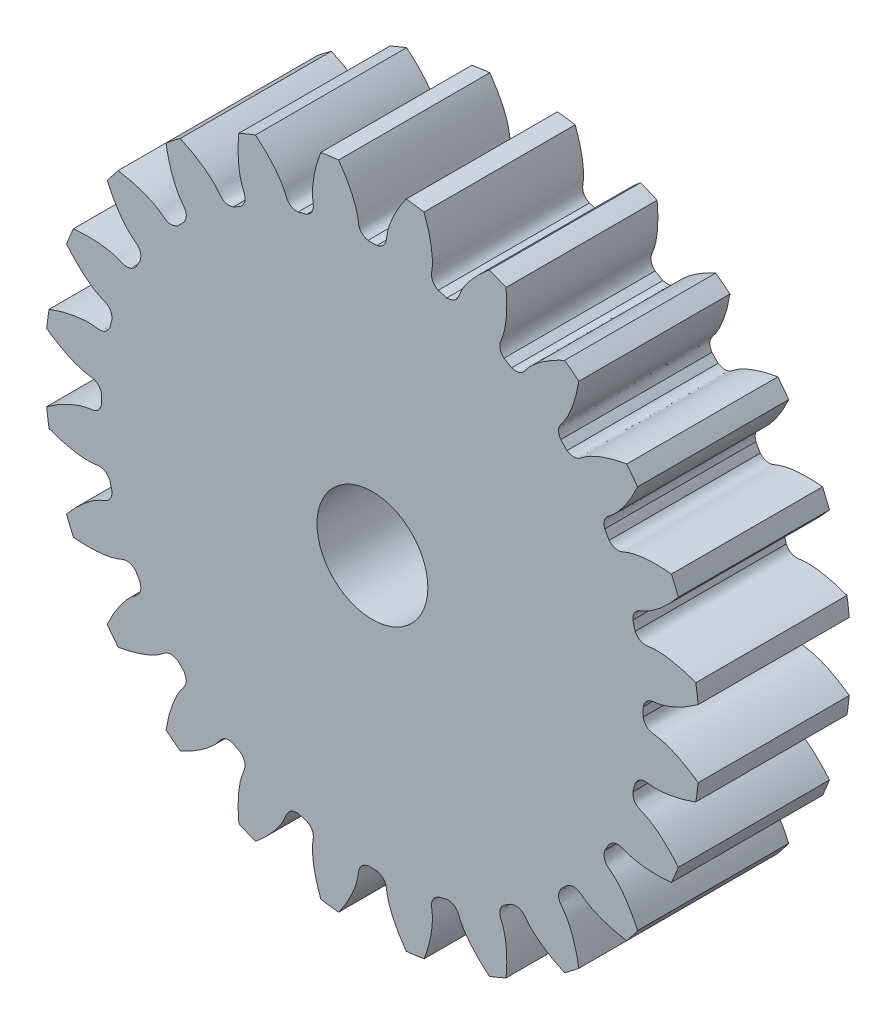
SolidWorks part; units mm, degrees
ref_plane "前视基准面" through (0, 0, 0) normal (0, 0, 1) x (1, 0, 0)
ref_plane "上视基准面" through (0, 0, 0) normal (0, 1, 0) x (1, 0, 0)
ref_plane "右视基准面" through (0, 0, 0) normal (1, 0, 0) x (0, 0, -1)
other "Configuration Table"
sketch "草图1" plane through (0, 0, 0) normal (0, 0, 1) x (1, 0, 0)
  circle A0 centre (0, 0) radius 6.5
extrude "凸台-拉伸1" add sketch "草图1" along normal blind 3
ref_axis "基准轴1" through (0, 0, 3) along (0, 0, -1)
sketch "草图2" plane through (0, 0, 0) normal (0, 0, 1) x (1, 0, 0)
  line L0 (0, 0) -> (0, 6.5) construction
  circle A0 centre (0, 0) radius 6.5 construction
  arc A1 (0.0884, 5.3743) -> (-0.0884, 5.3743) centre (0, 0) ccw
  arc A2 (1.5578, 7.3471) -> (-1.5578, 7.3471) centre (0, 0) ccw
  spline S0 degree 3 poles (0.0884, 5.3743) (0.284, 5.4284) (0.2695, 5.5579) (0.2931, 5.6863) (0.2965, 5.7029) (0.3007, 5.7216) (0.3058, 5.7424) (0.312, 5.7653) (0.3191, 5.7902) (0.3275, 5.8171) (0.3371, 5.846) (0.348, 5.8769) (0.3604, 5.9096) (0.3742, 5.9441) (0.3896, 5.9805) (0.4067, 6.0185) (0.4254, 6.0583) (0.446, 6.0997) (0.4684, 6.1427) (0.4928, 6.1872) (0.5192, 6.2332) (0.5476, 6.2806) (0.5782, 6.3293) (0.611, 6.3792) (0.6461, 6.4304) (0.6834, 6.4827) (0.7232, 6.536) (0.7654, 6.5903) (0.8101, 6.6456) (0.8574, 6.7016) (0.9073, 6.7583) (0.9598, 6.8158) (1.015, 6.8738) (1.0729, 6.9322) (1.1336, 6.9911) (1.1972, 7.0503) (1.2635, 7.1097) (1.3328, 7.1693) (1.4302, 7.2497) (1.506, 7.3084) (1.5578, 7.3471) knots 0 0 0 0 0.143961 0.149818 0.156577 0.164236 0.172796 0.182258 0.19262 0.203884 0.216049 0.229115 0.243082 0.25795 0.273719 0.290389 0.30796 0.326433 0.345806 0.366081 0.387257 0.409333 0.432311 0.45619 0.48097 0.506651 0.533234 0.560717 0.589101 0.618387 0.648574 0.679661 0.71165 0.74454 0.778331 0.813023 0.848616 0.885111 0.922506 1 1 1 1
  spline S1 degree 3 poles (-0.0884, 5.3743) (-0.284, 5.4284) (-0.2695, 5.5579) (-0.2931, 5.6863) (-0.2965, 5.7029) (-0.3007, 5.7216) (-0.3058, 5.7424) (-0.312, 5.7653) (-0.3191, 5.7902) (-0.3275, 5.8171) (-0.3371, 5.846) (-0.348, 5.8769) (-0.3604, 5.9096) (-0.3742, 5.9441) (-0.3896, 5.9805) (-0.4067, 6.0185) (-0.4254, 6.0583) (-0.446, 6.0997) (-0.4684, 6.1427) (-0.4928, 6.1872) (-0.5192, 6.2332) (-0.5476, 6.2806) (-0.5782, 6.3293) (-0.611, 6.3792) (-0.6461, 6.4304) (-0.6834, 6.4827) (-0.7232, 6.536) (-0.7654, 6.5903) (-0.8101, 6.6456) (-0.8574, 6.7016) (-0.9073, 6.7583) (-0.9598, 6.8158) (-1.015, 6.8738) (-1.0729, 6.9322) (-1.1336, 6.9911) (-1.1972, 7.0503) (-1.2635, 7.1097) (-1.3328, 7.1693) (-1.4302, 7.2497) (-1.506, 7.3084) (-1.5578, 7.3471) knots 0 0 0 0 0.143961 0.149818 0.156577 0.164236 0.172796 0.182258 0.19262 0.203884 0.216049 0.229115 0.243082 0.25795 0.273719 0.290389 0.30796 0.326433 0.345806 0.366081 0.387257 0.409333 0.432311 0.45619 0.48097 0.506651 0.533234 0.560717 0.589101 0.618387 0.648574 0.679661 0.71165 0.74454 0.778331 0.813023 0.848616 0.885111 0.922506 1 1 1 1
extrude "切除-拉伸1" cut sketch "草图2" along normal through all
pattern_circular "阵列(圆周)1" count 24 every 15 about axis through (0, 0, 3) along (0, 0, -1) of "切除-拉伸1"
sketch "草图3" plane through (0, 0, 0) normal (0, 0, 1) x (1, 0, 0)
  circle A0 centre (0, 0) radius 6 construction
  dimension "Dn" = 12
sketch "草图4" plane through (0, 0, 3) normal (0, 0, 1) x (1, 0, 0)
  circle A0 centre (0, 0) radius 1.1
  dimension "D1" = 2.2
extrude "切除-拉伸2" cut sketch "草图4" against normal up to next
